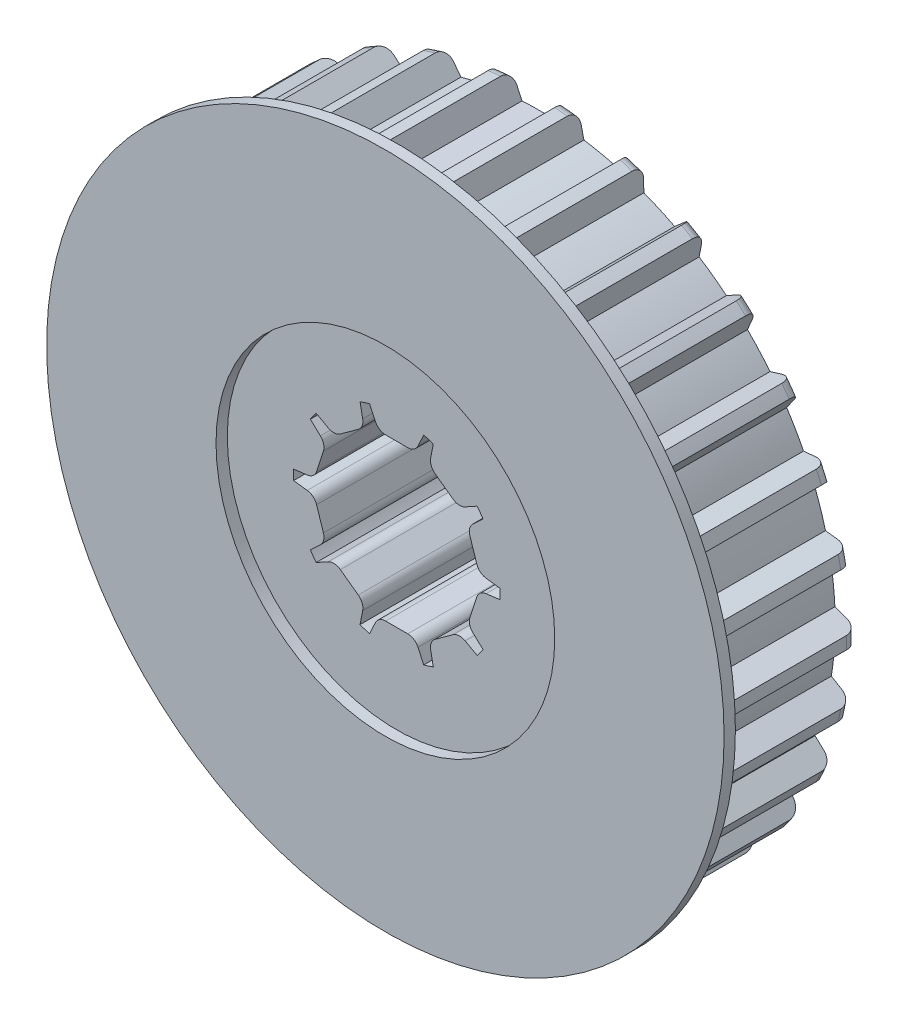
SolidWorks part; units mm, degrees
material "PMMA"
ref_plane "Ebene vorne" through (0, 0, 0) normal (0, 0, 1) x (1, 0, 0)
ref_plane "Ebene oben" through (0, 0, 0) normal (0, 1, 0) x (1, 0, 0)
ref_plane "Ebene rechts" through (0, 0, 0) normal (1, 0, 0) x (0, 0, -1)
ref_axis "Achse1" through (0, 0, 0.8815) along (0, 0, -1)
sketch "Skizze1" plane through (0, 0, 0) normal (1, 0, 0) x (0, 0, -1)
  line L0 (0, 31.7827) -> (0, -32.6712) construction
  line L1 (-33.2769, 0) -> (37.2346, 0) construction
  line L2 (0, 4.57) -> (0, 14.12)
  line L3 (0, 14.12) -> (5.8, 14.12)
  line L4 (6.3, 13.62) -> (6.3, 6.1)
  line L6 (7.1, 6.1) -> (7.1, 4.57)
  line L7 (7.1, 4.57) -> (0, 4.57)
  line L8 (7.1, 6.1) -> (6.3, 6.1)
  arc A1 (5.8, 14.12) -> (6.3, 13.62) centre (5.8, 13.62) cw
  point P19 (6.3, 14.12)
  dimension "D8" = 0.5
  dimension "D1" = 6.3
  dimension "D2" = 28.24
  dimension "D3" = 0.8
  dimension "D5" = 6.1
  dimension "D7" = 9.14
revolve "Rotation1" add sketch "Skizze1" angle 360 about L1
sketch "Skizze2" plane through (0, 0, 0) normal (0, 0, 1) x (1, 0, 0)
  line L0 (0, 25.2337) -> (0, -18.8875) construction
  line L1 (18.5217, 0) -> (-21.6513, 0) construction
  line L2 (0.7476, 13.0987) -> (1.2, 14.0689)
  line L3 (-0.7476, 13.0987) -> (-1.2, 14.0689)
  circle A0 centre (0, 0) radius 14.12 construction
  circle A1 centre (0, 0) radius 13.12 construction
  circle A2 centre (0, 0) radius 14.12 construction
  arc A3 (0.7476, 13.0987) -> (-0.7476, 13.0987) centre (0, 0) ccw
  arc A4 (1.2, 14.0689) -> (-1.2, 14.0689) centre (0, 0) ccw
  dimension "D1" = 26.24
  dimension "D2" = 50
  dimension "D3" = 2.4
  dimension "D4" = 1.4951
extrude "Schnitt-Linear austragen1" cut sketch "Skizze2" against normal through all
pattern_circular "Kreismuster1" count 30 over 360 about axis through (0, 0, 0.8815) along (0, 0, -1) of "Schnitt-Linear austragen1"
sketch "Skizze3" plane through (0, 0, 0) normal (0, 0, 1) x (1, 0, 0)
  line L0 (0, 18.7184) -> (0, -16.4301) construction
  line L1 (17.9538, 0) -> (-20.4113, 0) construction
  line L2 (0.8085, 3.57) -> (1.2, 4.4096)
  line L3 (-0.8085, 3.57) -> (-1.2, 4.4096)
  line L4 (0.8085, 3.57) -> (-0.8085, 3.57)
  line L5 (-2.5176, 4.57) -> (3.1687, 4.57) construction
  circle A0 centre (0, 0) radius 4.57 construction
  circle A2 centre (0, 0) radius 4.57 construction
  arc A3 (1.2, 4.4096) -> (-1.2, 4.4096) centre (0, 0) ccw
  dimension "D1" = 9.14
  dimension "D2" = 1
  dimension "D3" = 50
  dimension "D4" = 2.4
  dimension "D5" = 1.6169
extrude "Aufsatz-Linear austragen1" add sketch "Skizze3" against normal up to surface (7.1 mm away) up to face at (6.1, 0, -7.1)
fillet "Verrundung1" radius 0.5 2 edges at (0.8085, 3.57, -3.55) (-0.8085, 3.57, -3.55)
pattern_circular "Kreismuster2" count 10 over 360 about axis through (0, 0, 0.8815) along (0, 0, -1) of "Aufsatz-Linear austragen1", "Verrundung1"
sketch "Skizze4" plane through (0, 0, 0) normal (1, 0, 0) x (0, 0, -1)
  line L0 (0, 19.3542) -> (0, -18.0091) construction
  line L1 (-12.7482, 0) -> (17.6163, 0) construction
  line L2 (0, 7.5) -> (-0.5, 7.5)
  line L3 (-0.5, 7.5) -> (-0.5, 15)
  line L4 (-0.5, 15) -> (0, 15)
  line L5 (0, 15) -> (0, 14.25)
  line L6 (0, 14.25) -> (0.6536, 13.5964)
  line L7 (0.8, 13.2429) -> (0.8, 13)
  line L8 (0.8, 13) -> (0, 13)
  line L9 (0, 13) -> (0, 7.5)
  arc A0 (0.8, 13.2429) -> (0.6536, 13.5964) centre (0.3, 13.2429) ccw
  dimension "D8" = 0.5
  dimension "D1" = 15
  dimension "D2" = 0.5
  dimension "D3" = 30
  dimension "D4" = 14.25
  dimension "D5" = 45
  dimension "D6" = 0.8
  dimension "D7" = 13
revolve "Rotation2" add sketch "Skizze4" angle 360 about L1
sketch "Skizze5" plane through (0, 0, 0) normal (1, 0, 0) x (0, 0, -1)
  line L0 (13.5237, 0) -> (-4.1574, 0) construction
  line L1 (0, -18.0539) -> (0, 17.4561) construction
  line L2 (7.1, 4.2) -> (6.3, 5)
  line L3 (6.3, 5) -> (6.3, 6.1)
  line L4 (6.3, 6.1) -> (7.1, 6.1)
  line L5 (7.1, 6.1) -> (7.1, 4.2)
  line L6 (6.3, -6.1) -> (6.3, 6.1) construction
  line L7 (7.1, -6.1) -> (7.1, 6.1) construction
  line L8 (7.1, 6.1) -> (6.3, 6.1) construction
  dimension "D1" = 135
  dimension "D2" = 5
revolve "Schnitt-Rotation1" cut sketch "Skizze5" angle 360 about L0
fillet "Verrundung2" radius 0.5 10 edges at (2.4687, 3.3979, -7.1) (0, 4.2, -7.1) (-2.4687, 3.3979, -7.1) (-3.9944, 1.2979, -7.1) (-3.9944, -1.2979, -7.1) (-2.4687, -3.3979, -7.1) (3.9944, 1.2979, -7.1) (3.9944, -1.2979, -7.1) (2.4687, -3.3979, -7.1) (0, -4.2, -7.1)
